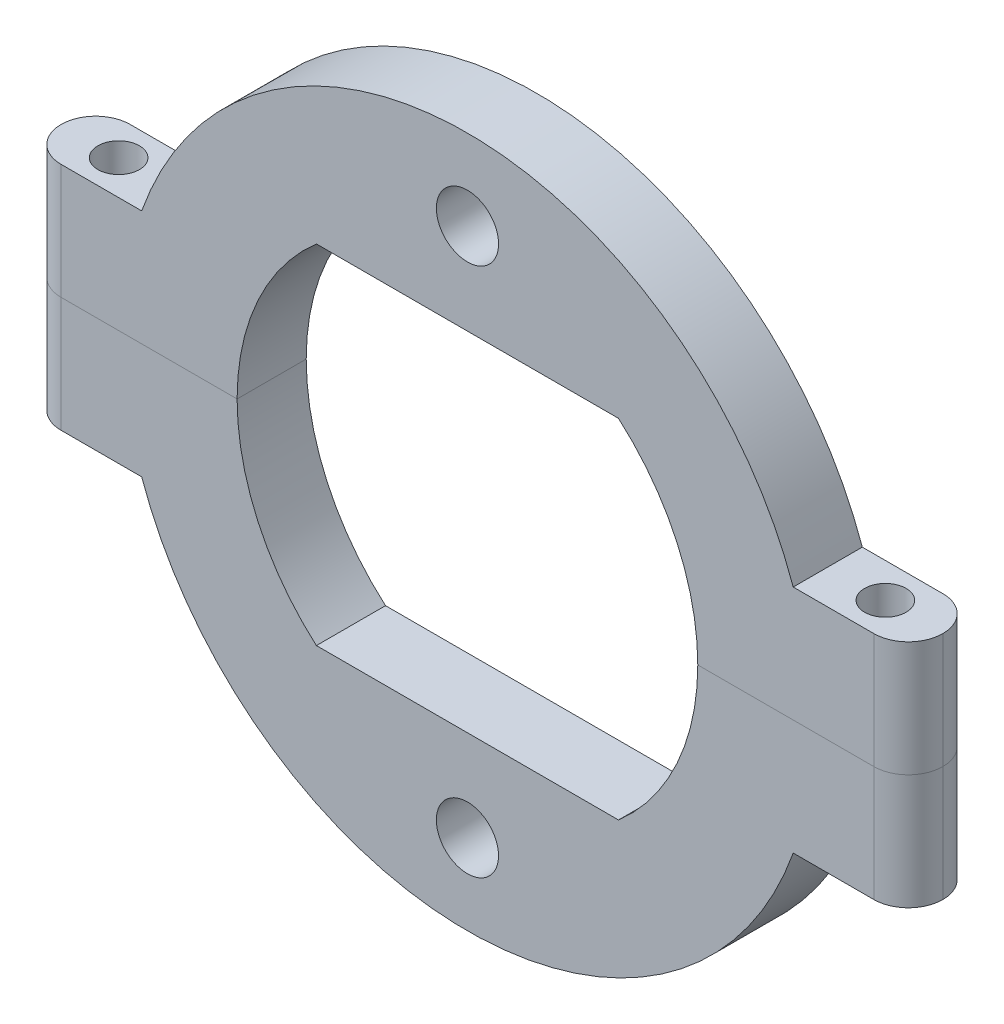
SolidWorks part; units mm, degrees
ref_plane "Front Plane" through (0, 0, 0) normal (0, 0, 1) x (1, 0, 0)
ref_plane "Top Plane" through (0, 0, 0) normal (0, 1, 0) x (1, 0, 0)
ref_plane "Right Plane" through (0, 0, 0) normal (1, 0, 0) x (0, 0, -1)
sketch "Sketch1" plane through (0, 0, 0) normal (0, 0, 1) x (1, 0, 0)
  line L0 (-6.5572, 7.55) -> (6.5572, 7.55)
  line L1 (-6.5572, -7.55) -> (6.5572, -7.55)
  line L2 (0, -55) -> (0, 55) construction
  line L3 (-14.1421, 5) -> (-19.1421, 5)
  line L4 (-14.1421, 5) -> (-14.1421, -5)
  line L5 (-14.1421, -5) -> (-19.1421, -5)
  line L6 (-19.1421, 5) -> (-19.1421, -5)
  line L7 (-16.6421, -5) -> (-16.6421, 5) construction
  line L8 (-14.1421, 0) -> (-19.1421, 0) construction
  line L9 (14.1421, -5) -> (19.1421, -5)
  line L10 (19.1421, 5) -> (19.1421, -5)
  line L11 (14.1421, 5) -> (19.1421, 5)
  line L12 (14.1421, 5) -> (14.1421, -5)
  circle A0 centre (0, 0) radius 10
  circle A1 centre (0, 0) radius 15
  point P356 (-16.6421, 0)
  dimension "D1" = 20
  dimension "D2" = 30
  dimension "D3" = 15.1
  dimension "D4" = 5
  dimension "D5" = 10
extrude "Boss-Extrude1" add sketch "Sketch1" along normal blind 3 contours A1 A0 | L0 A0 | L1 A0 | A1 L9 L10 L11 | L12 A1 | L4 A1 | A1 L3 L6 L5 region at (0, 8.5411, 0) region at (0, -8.5411, 0) region at (-16.9224, 0, 0) region at (0, 14.5877, 0) region at (-14.4861, 0, 0) region at (14.4861, 0, 0) region at (16.9224, 0, 0)
sketch "Sketch2" plane through (0, -5, 0) normal (0, -1, 0) x (1, 0, 0)
  line L0 (19.1421, 3) -> (19.1421, 0) construction
  line L1 (14.1421, 0) -> (19.1421, 0) construction
  circle A0 centre (16.6421, 1.5) radius 0.9
  dimension "D1" = 1.8
  dimension "D2" = 2.5
  dimension "D3" = 1.5
extrude "Cut-Extrude1" cut sketch "Sketch2" against normal through all
mirror "Mirror1" about plane through (0, 0, 0) normal (1, 0, 0) of "Cut-Extrude1"
sketch "Sketch3" plane through (0, 0, 3) normal (0, 0, 1) x (1, 0, 0)
  line L0 (0, 11.5) -> (0, 0) construction
  line L2 (1.65, 0) -> (-1.65, 0) construction
  circle A3 centre (0, 11.5) radius 1.35
  circle A4 centre (0, -11.5) radius 1.35
  dimension "D1" = 2.7
  dimension "D2" = 11.5
extrude "Cut-Extrude2" cut sketch "Sketch3" against normal through all
fillet "Fillet2" radius 1.5 4 edges at (19.1421, 0, 3) (19.1421, 0, 0) (-19.1421, 0, 3) (-19.1421, 0, 0)
split "Split1" trim tools "Top Plane" bodies to split 104 resulting bodies 105 106
